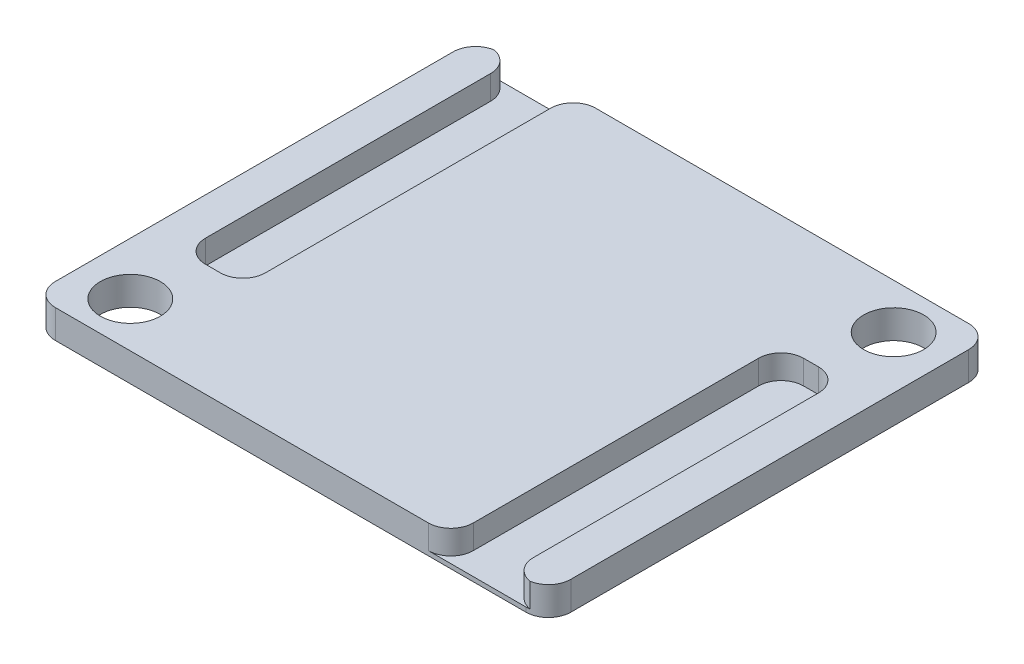
SolidWorks part; units mm, degrees
material "aluminio"
ref_plane "Alzado" through (0, 0, 0) normal (0, 0, 1) x (1, 0, 0)
ref_plane "Planta" through (0, 0, 0) normal (0, 1, 0) x (1, 0, 0)
ref_plane "Vista lateral" through (0, 0, 0) normal (1, 0, 0) x (0, 0, -1)
sketch "Croquis1" plane through (0, 0, 0) normal (0, 1, 0) x (1, 0, 0)
  line L0 (0, 0) -> (34.35, 0)
  line L2 (0, 29.5) -> (34.35, 29.5)
  line L3 (25.85, 3) -> (8.85, 3) construction
  line L4 (25.85, 3) -> (25.85, 26.5) construction
  line L5 (25.85, 26.5) -> (8.85, 26.5) construction
  line L6 (8.85, 3) -> (8.85, 26.5) construction
  line L7 (0, 29.5) -> (0, 0)
  line L12 (34.35, 0) -> (34.35, 29.5)
  circle A0 centre (3.5, 3) radius 2
  circle A1 centre (30.85, 26.5) radius 2
  dimension "D3" = 4
  dimension "D2" = 29.5
  dimension "D4" = 3.5
  dimension "D5" = 3
  dimension "D6" = 27.35
  dimension "D7" = 23.5
  dimension "D8" = 3
  dimension "D9" = 3.5
  dimension "D10" = 3
  dimension "D11" = 8.5
  dimension "D12" = 8.85
extrude "Saliente-Extruir1" add sketch "Croquis1" along normal blind 1.9
sketch "Croquis2" plane through (0, 1.9, 0) normal (0, 1, 0) x (1, 0, 0)
  line L0 (0, 0) -> (34.35, 0) construction
  line L1 (27.85, 22) -> (31.85, 22)
  line L2 (27.85, 22) -> (27.85, 0)
  line L3 (27.85, 0) -> (31.85, 0)
  line L4 (31.85, 22) -> (31.85, 0)
  line L5 (34.35, 0) -> (34.35, 29.5) construction
  line L6 (34.35, 29.5) -> (0, 29.5) construction
  line L7 (2.5, 29.5) -> (6.5, 29.5)
  line L8 (2.5, 29.5) -> (2.5, 7.5)
  line L9 (2.5, 7.5) -> (6.5, 7.5)
  line L10 (6.5, 29.5) -> (6.5, 7.5)
  line L11 (0, 29.5) -> (0, 0) construction
  dimension "D1" = 4
  dimension "D2" = 2.5
  dimension "D3" = 22
  dimension "D4" = 4
  dimension "D5" = 2.5
  dimension "D6" = 22
extrude "Cortar-Extruir2" cut sketch "Croquis2" against normal blind 1.6
fillet "Redondeo1" radius 1.5 12 edges at (0, 0.95, -29.5) (0, 0.95, 0) (34.35, 0.95, -29.5) (34.35, 0.95, 0) (31.85, 1.1, -22) (31.85, 1.1, 0) (27.85, 1.1, 0) (27.85, 1.1, -22) (2.5, 1.1, -7.5) (2.5, 1.1, -29.5) (6.5, 1.1, -29.5) (6.5, 1.1, -7.5)
